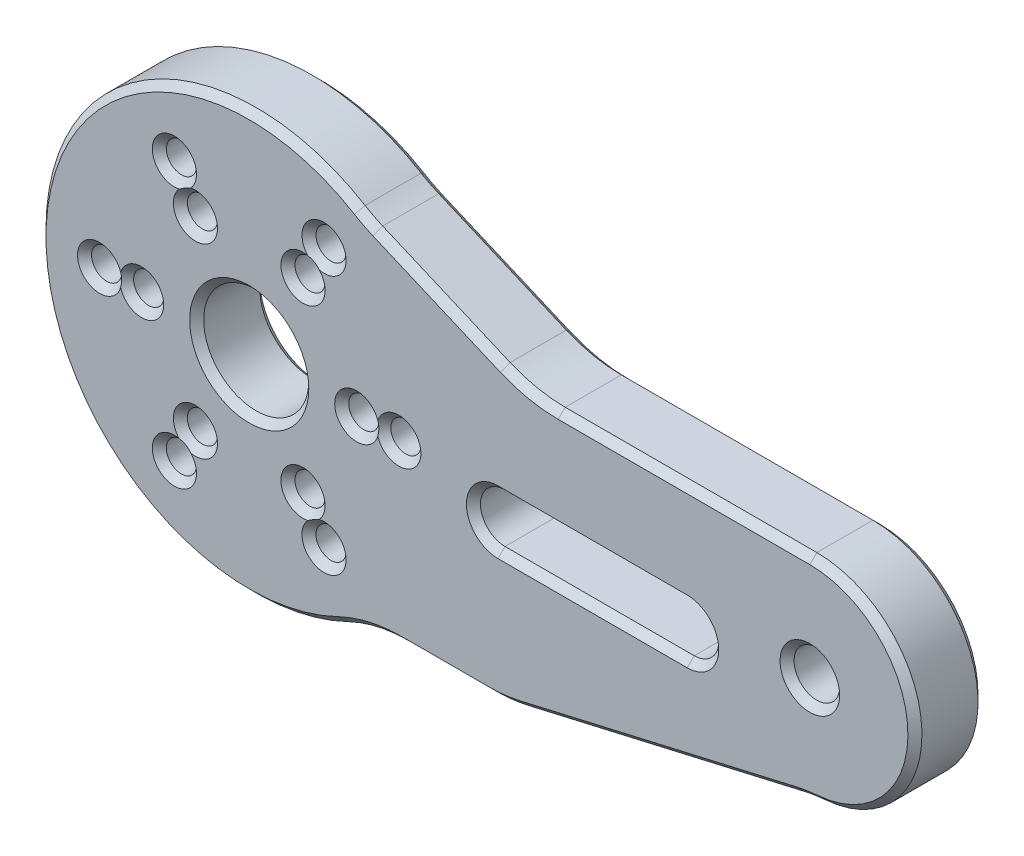
SolidWorks part; units mm, degrees
ref_plane "前视基准面" through (0, 0, 0) normal (0, 0, 1) x (1, 0, 0)
ref_plane "上视基准面" through (0, 0, 0) normal (0, 1, 0) x (1, 0, 0)
ref_plane "右视基准面" through (0, 0, 0) normal (1, 0, 0) x (0, 0, -1)
sketch "草图1" plane through (0, 0, 0) normal (0, 0, 1) x (1, 0, 0)
  line L0 (15, 0.25) -> (1.5, 0.25)
  line L1 (1.5, -3.25) -> (15, -3.25)
  line L2 (3.1493, -12.2449) -> (22.8754, -7.7014)
  line L3 (-5.3528, -12.5) -> (0.9048, -12.5)
  line L4 (1.8685, 8.3035) -> (-7.2262, 12.1873)
  line L5 (23.75, 7.5) -> (5.7958, 7.5)
  arc A0 (1.5, 0.25) -> (1.5, -3.25) centre (1.5, -1.5) ccw
  arc A1 (15, -3.25) -> (15, 0.25) centre (15, -1.5) ccw
  circle A2 centre (23.75, 0) radius 1.625
  circle A3 centre (-5.575, 0) radius 1.075
  circle A4 centre (-8.575, 0) radius 1.075
  circle A5 centre (-16.25, 0) radius 3.75
  circle A6 centre (-12.4125, -6.6467) radius 1.075
  circle A7 centre (-10.9125, -9.2448) radius 1.075
  circle A8 centre (-20.0875, -6.6467) radius 1.075
  circle A9 centre (-21.5875, -9.2448) radius 1.075
  circle A10 centre (-23.925, 0) radius 1.075
  circle A11 centre (-26.925, 0) radius 1.075
  circle A12 centre (-20.0875, 6.6467) radius 1.075
  circle A13 centre (-21.5875, 9.2448) radius 1.075
  circle A14 centre (-12.4125, 6.6467) radius 1.075
  circle A15 centre (-10.9125, 9.2448) radius 1.075
  arc A16 (24.3371, -7.477) -> (22.8754, -7.7014) centre (25.1199, -17.4463) ccw
  arc A17 (24.3371, -7.477) -> (23.75, 7.5) centre (23.75, 0) ccw
  arc A18 (0.9048, -12.5) -> (3.1493, -12.2449) centre (0.9048, -2.5) ccw
  arc A19 (-5.3528, -12.5) -> (-9.7117, -13.5) centre (-5.3528, -22.5) ccw
  arc A20 (-8.4793, 12.8303) -> (-9.7117, -13.5) centre (-16.25, 0) ccw
  arc A21 (-8.4793, 12.8303) -> (-7.2262, 12.1873) centre (-3.2989, 21.3838) ccw
  arc A22 (1.8685, 8.3035) -> (5.7958, 7.5) centre (5.7958, 17.5) ccw
extrude "凸台-拉伸1" add sketch "草图1" along normal blind 5
chamfer "倒角1" distance 0.5 angle 45 58 edges at (-9.8375, 9.2448, 0) (-11.3375, 6.6467, 0) (-20.5125, 9.2448, 0) (-19.0125, 6.6467, 0) (-25.85, 0, 0) (-22.85, 0, 0) (-20.5125, -9.2448, 0) (-19.0125, -6.6467, 0) (-9.8375, -9.2448, 0) (-11.3375, -6.6467, 0) (-12.5, 0, 0) (-7.5, 0, 0) (-4.5, 0, 0) (25.375, 0, 0) (8.25, 0.25, 0) (16.75, -1.5, 0) (8.25, -3.25, 0) (-0.25, -1.5, 0) (14.7729, 7.5, 0) (3.7915, 7.7029, 0) (-2.6788, 10.2454, 0) (-7.8641, 12.4867, 0) (-31.2336, 0.7013, 0) (-7.5888, -12.7532, 0) (-2.224, -12.5, 0) (2.0343, -12.436, 0) (13.0124, -9.9732, 0) (23.6021, -7.5622, 0) (31.2442, 0.2938, 0) (-9.8375, 9.2448, 5) (-20.5125, 9.2448, 5) (-25.85, 0, 5) (-20.5125, -9.2448, 5) (-9.8375, -9.2448, 5) (-12.5, 0, 5) (-4.5, 0, 5) (16.75, -1.5, 5) (8.25, 0.25, 5) (-0.25, -1.5, 5) (8.25, -3.25, 5) (23.6021, -7.5622, 5) (13.0124, -9.9732, 5) (2.0343, -12.436, 5) (-2.224, -12.5, 5) (-7.5888, -12.7532, 5) (-31.2336, 0.7013, 5) (-7.8641, 12.4867, 5) (-2.6788, 10.2454, 5) (3.7915, 7.7029, 5) (14.7729, 7.5, 5) (31.2442, 0.2938, 5) (25.375, 0, 5) (-7.5, 0, 5) (-11.3375, -6.6467, 5) (-19.0125, -6.6467, 5) (-22.85, 0, 5) (-19.0125, 6.6467, 5) (-11.3375, 6.6467, 5)
ref_plane "基准面1" through (0, 0, 0) normal (0, 0, -1) x (-1, 0, 0)
